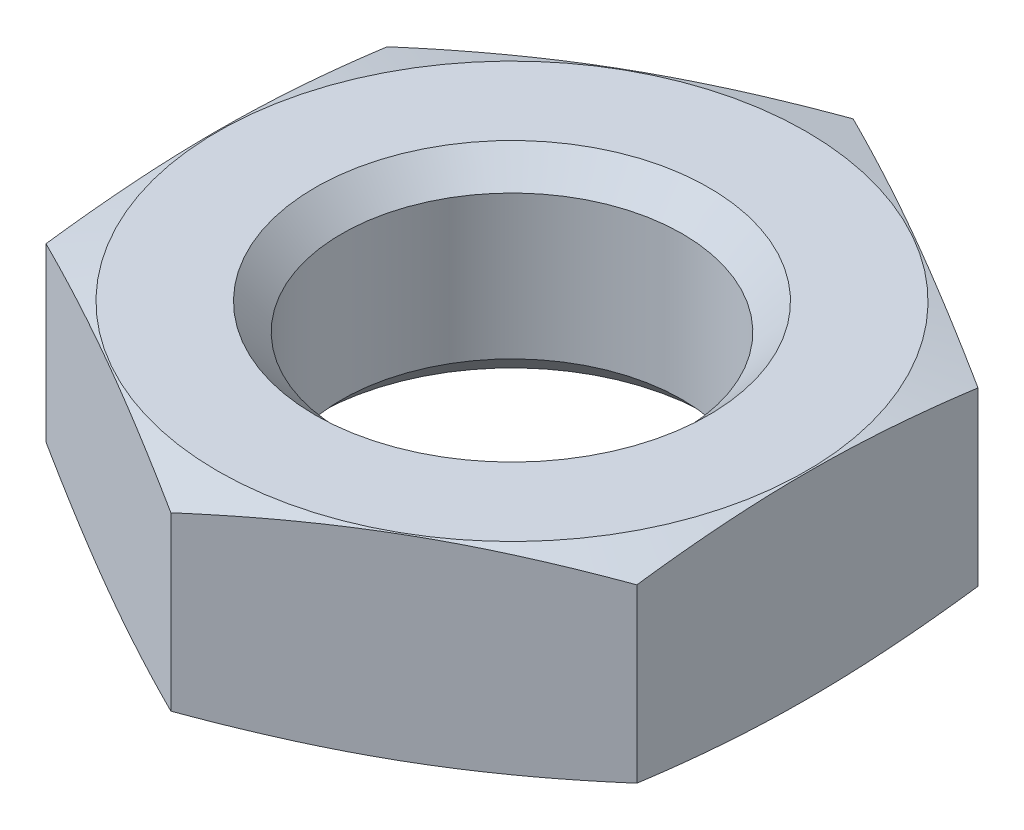
SolidWorks part; units mm, degrees
ref_plane "Front Plane" through (0, 0, 0) normal (0, 0, 1) x (1, 0, 0)
ref_plane "Top Plane" through (0, 0, 0) normal (0, 1, 0) x (1, 0, 0)
ref_plane "Right Plane" through (0, 0, 0) normal (1, 0, 0) x (0, 0, -1)
ref_plane "Plane1" through (0, 0, 0) normal (0, 0, 1) x (1, 0, 0)
sketch "Sketch1" plane through (0, 0, 0) normal (0, 0, 1) x (1, 0, 0)
  line L0 (0, 0) -> (11.95, 0)
  line L1 (11.95, 0) -> (26.8782, -4)
  line L2 (26.8782, -4) -> (11.95, -8)
  line L3 (11.95, -8) -> (0, -8)
  line L4 (0, -8) -> (0, 0)
  line L5 (0, -8) -> (0, 0) construction
revolve "Revolve1" add sketch "Sketch1" angle 360 about L5
ref_plane "Plane2" through (0, 0, 0) normal (0, 1, 0) x (1, 0, 0)
sketch "Sketch2" plane through (0, 0, 0) normal (0, 1, 0) x (1, 0, 0)
  line L0 (-48, 48) -> (-48, -48)
  line L1 (-48, -48) -> (48, -48)
  line L2 (48, -48) -> (48, 48)
  line L3 (48, 48) -> (-48, 48)
  line L4 (-12, -6.9282) -> (0, -13.8564)
  line L5 (0, -13.8564) -> (12, -6.9282)
  line L6 (12, -6.9282) -> (12, 6.9282)
  line L7 (12, 6.9282) -> (0, 13.8564)
  line L8 (0, 13.8564) -> (-12, 6.9282)
  line L9 (-12, 6.9282) -> (-12, -6.9282)
extrude "Cut-Extrude1" cut sketch "Sketch2" against normal blind 9 and the other way blind 9
ref_plane "Plane3" through (0, 0, 0) normal (0, 0, 1) x (1, 0, 0)
sketch "Sketch3" plane through (0, 0, 0) normal (0, 0, 1) x (1, 0, 0)
  line L0 (0, 0) -> (8, 0)
  line L1 (8, 0) -> (6.9175, -1.0825)
  line L2 (6.9175, -1.0825) -> (6.9175, -6.9175)
  line L3 (6.9175, -6.9175) -> (8, -8)
  line L4 (8, -8) -> (0, -8)
  line L5 (0, -8) -> (0, 0)
  line L6 (0, -8) -> (0, 0) construction
revolve "Cut-Revolve1" cut sketch "Sketch3" angle 360 about L6 reverse direction yes
cosmetic thread "Cosmetic Thread1" parameters "D1"=8, "D2"=16
